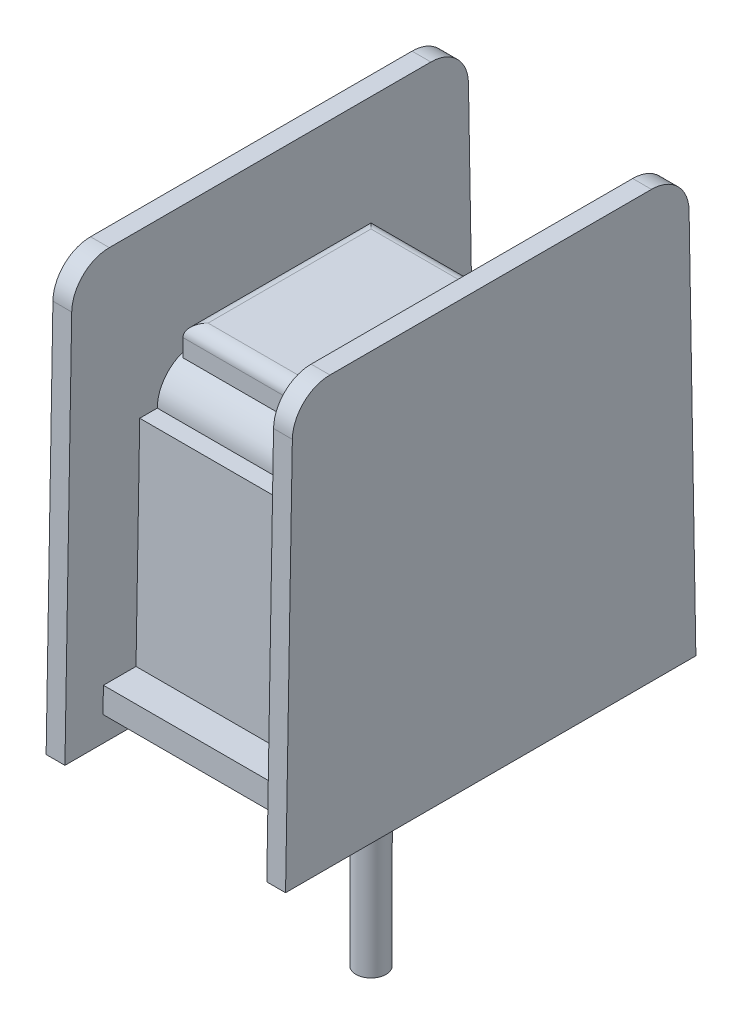
SolidWorks part; units mm, degrees
ref_plane "前视基准面" through (0, 0, 0) normal (0, 0, 1) x (1, 0, 0)
ref_plane "上视基准面" through (0, 0, 0) normal (0, 1, 0) x (1, 0, 0)
ref_plane "右视基准面" through (0, 0, 0) normal (1, 0, 0) x (0, 0, -1)
sketch "草图1" plane through (0, 0, 0) normal (0, 1, 0) x (1, 0, 0)
  line L0 (0, 14.1902) -> (0, -10.6155) construction
  line L1 (-22.4154, 0) -> (19.6333, 0) construction
  line L3 (-4.775, 8) -> (4.775, 8)
  line L4 (-4.775, 8) -> (-4.775, -8)
  line L5 (-4.775, -8) -> (4.775, -8)
  line L6 (4.775, 8) -> (4.775, -8)
  dimension "D1" = 9.55
  dimension "D2" = 16
extrude "拉伸1" add sketch "草图1" along normal blind 17
sketch "草图2" plane through (0, 17, 0) normal (0, 1, 0) x (-1, 0, 0)
  line L1 (4.775, 8) -> (-4.775, 8) construction
  line L2 (-4.025, 8) -> (4.025, 8)
  line L3 (-4.025, 8) -> (-4.025, -8)
  line L4 (-4.025, -8) -> (4.025, -8)
  line L8 (4.025, 8) -> (4.025, -8)
  line L9 (-4.775, -8) -> (4.775, -8) construction
  line L10 (4.775, -8) -> (4.775, 8) construction
  line L11 (-4.775, 8) -> (-4.775, -8) construction
  dimension "D1" = 0.75
  dimension "D2" = 0.75
extrude "切除-拉伸1" cut sketch "草图2" against normal blind 6.5
sketch "草图5" plane through (0, 0, -8) normal (0, 0, -1) x (-1, 0, 0)
  line L0 (-4.775, 0) -> (4.775, 0) construction
  line L1 (-4.025, 10.5) -> (4.025, 10.5)
  line L2 (-4.025, 10.5) -> (-4.025, 2)
  line L3 (-4.025, 2) -> (4.025, 2)
  line L4 (4.025, 10.5) -> (4.025, 2)
  dimension "D1" = 2
extrude "切除-拉伸4" cut sketch "草图5" against normal blind 2.8
sketch "草图6" plane through (0, 0, -8) normal (0, 0, -1) x (-1, 0, 0)
  line L0 (-4.775, 0) -> (4.775, 0) construction
  line L1 (-4.025, 2) -> (4.025, 2)
  line L2 (-4.025, 2) -> (-4.025, 0)
  line L3 (-4.025, 0) -> (4.025, 0)
  line L4 (4.025, 2) -> (4.025, 0)
extrude "切除-拉伸5" cut sketch "草图6" against normal blind 1.5
mirror "镜向3" about plane through (0, 0, 0) normal (0, 0, 1) of "切除-拉伸4", "切除-拉伸5"
draft "拔模1" type of draft neutral plane draft angle 1 faces to draft 8 face at (4.4, 8.5, 8) face at (-4.4, 8.5, 8) face at (0, 1, 6.5) face at (0, 6.25, 5.2) face at (0, 1, -6.5) face at (-4.4, 8.5, -8) face at (0, 6.25, -5.2) face at (4.4, 8.5, -8) neutral plane through (4.025, 10.5, -8) neutral plane normal (0, 1, 0) parameters "D1"=1
sketch "草图7" plane through (0, 0, 0) normal (0, -1, 0) x (1, 0, 0)
  line L1 (4.025, 6.6833) -> (-4.025, 6.6833)
  line L2 (4.025, 6.6833) -> (4.025, -6.6833)
  line L3 (4.025, -6.6833) -> (-4.025, -6.6833)
  line L4 (-4.025, 6.6833) -> (-4.025, -6.6833)
extrude "切除-拉伸6" cut sketch "草图7" against normal blind 1
fillet "圆角1" radius 1.5 4 edges at (4.4, 17, 7.8865) (-4.4, 17, 7.8865) (-4.4, 17, -7.8865) (4.4, 17, -7.8865)
sketch "草图8" plane through (0, 10.5, 0) normal (0, 1, 0) x (-1, 0, 0)
  line L0 (-4.025, 5.2) -> (-4.025, -5.2) construction
  line L1 (-4.025, -4.5) -> (4.025, -4.5)
  line L2 (-4.025, -4.5) -> (-4.025, 4.5)
  line L3 (-4.025, 4.5) -> (4.025, 4.5)
  line L4 (4.025, -4.5) -> (4.025, 4.5)
  line L5 (4.025, -6.4125) -> (4.025, 6.4125) construction
  line L6 (5.894, 0) -> (-6.1893, 0) construction
  dimension "D1" = 9
extrude "卡片" add sketch "草图8" along normal blind 1.5
sketch "草图9" plane through (0, 1, 0) normal (0, -1, 0) x (1, 0, 0)
  circle A0 centre (0, 0) radius 0.6
  dimension "D1" = 1.2
extrude "拉伸3" add sketch "草图9" along normal blind 10
fillet "圆角2" radius 1.5 2 edges at (0, 12, -4.5) (0, 12, 4.5)
sketch "草图10" plane through (0, 12, 0) normal (0, 1, 0) x (-1, 0, 0)
  line L1 (0, 8.0097) -> (0, -7.6912) construction
  line L2 (-3.75, 3.75) -> (3.75, 3.75)
  line L3 (-3.75, 3.75) -> (-3.75, -3.75)
  line L4 (-3.75, -3.75) -> (3.75, -3.75)
  line L6 (-6.3124, 0) -> (6.1893, 0) construction
  line L7 (3.75, 3.75) -> (3.75, -3.75)
  dimension "D1" = 7.5
  dimension "D2" = 7.5
extrude "拉伸4" add sketch "草图10" along normal blind 1.2
fillet "圆角4" radius 0.5 4 edges at (3.75, 13.2, 0) (-3.75, 13.2, 0) (0, 13.2, -3.75) (0, 13.2, 3.75)
